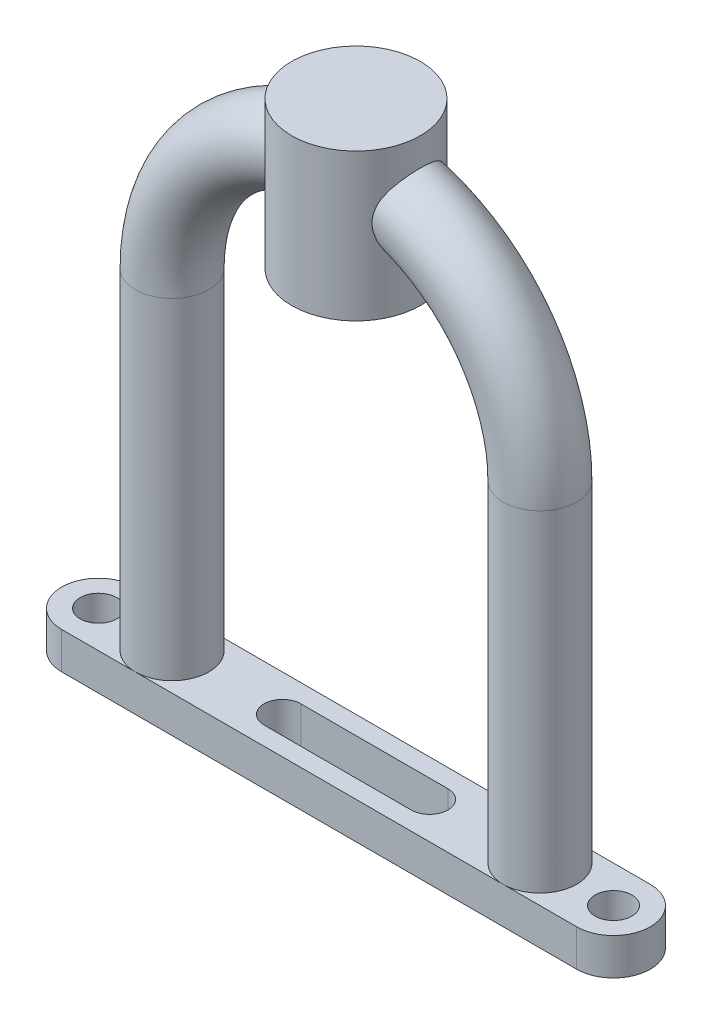
SolidWorks part; units mm, degrees
ref_plane "Plano frontal" through (0, 0, 0) normal (0, 0, 1) x (1, 0, 0)
ref_plane "Plano superior" through (0, 0, 0) normal (0, 1, 0) x (1, 0, 0)
ref_plane "Plano direito" through (0, 0, 0) normal (1, 0, 0) x (0, 0, -1)
sketch "Esboço1" plane through (0, 0, 0) normal (0, 1, 0) x (1, 0, 0)
  line L0 (-3.5, 0) -> (3.5, 0) construction
  line L1 (-3.5, 0.5) -> (3.5, 0.5)
  line L2 (-3.5, -0.5) -> (3.5, -0.5)
  line L3 (-1, 0) -> (1, 0) construction
  line L4 (-1, 0.25) -> (1, 0.25)
  line L5 (-1, -0.25) -> (1, -0.25)
  arc A0 (-3.5, 0.5) -> (-3.5, -0.5) centre (-3.5, 0) ccw
  arc A1 (3.5, -0.5) -> (3.5, 0.5) centre (3.5, 0) ccw
  circle A2 centre (3.5, 0) radius 0.25
  circle A3 centre (-3.5, 0) radius 0.25
  arc A4 (-1, 0.25) -> (-1, -0.25) centre (-1, 0) ccw
  arc A5 (1, -0.25) -> (1, 0.25) centre (1, 0) ccw
  point P2 (0, 0)
  point P14 (0, 0)
  point P19 (0, 0)
  dimension "D3" = 0.5
  dimension "D4" = 0.5
  dimension "D1" = 3.5
  dimension "D2" = 1
  dimension "D5" = 2
  dimension "D6" = 0.5
extrude "Ressalto-extrusão1" add sketch "Esboço1" along normal mid plane 0.5
sketch "Esboço2" plane through (0, 0, 0) normal (0, 0, 1) x (1, 0, 0)
  line L0 (-1, 0.25) -> (-2.5, 0.25) construction
  line L1 (3.5, 0.25) -> (-3.5, 0.25) construction
  line L2 (-2.5, 0.25) -> (-2.5, 4.75)
  line L3 (-2.5, 4.75) -> (0, 4.75) construction
  line L4 (2.5, 4.75) -> (2.5, 0.25)
  arc A0 (-2.5, 4.75) -> (2.5, 4.75) centre (0, 4.75) cw
  dimension "D1" = 4.5
sketch "Esboço3" plane through (0, 0.25, 0) normal (0, 1, 0) x (1, 0, 0)
  line L0 (-2.5, 0) -> (0, 0) construction
  line L1 (-1, 0) -> (-2.5, 0) construction
  circle A0 centre (-2.5, 0) radius 0.5
sweep "Varredura1" add profiles "Esboço3" path "Esboço2"
ref_plane "Plano1" through (0, 8, 0) normal (0, 1, 0) x (1, 0, 0)
sketch "Esboço4" plane through (0, 8, 0) normal (0, 1, 0) x (1, 0, 0)
  circle A0 centre (0, 0) radius 0.875
  point P3 (0, 0)
extrude "Ressalto-extrusão4" add sketch "Esboço4" against normal blind 2 separate body
sketch "Esboço6" plane through (0, 8, 0) normal (0, 1, 0) x (1, 0, 0)
  circle A0 centre (0, 0) radius 0.5
